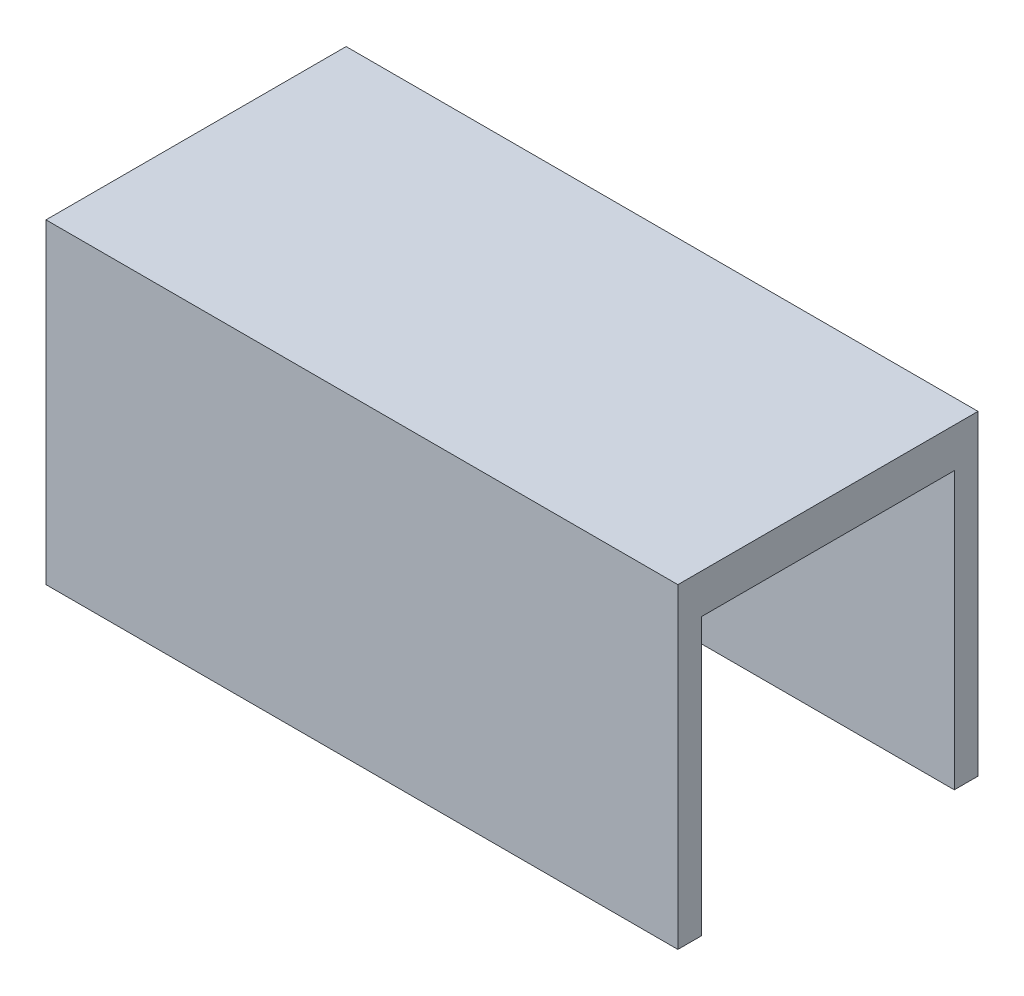
SolidWorks part; units mm, degrees
ref_plane "Front Plane" through (0, 0, 0) normal (0, 0, 1) x (1, 0, 0)
ref_plane "Top Plane" through (0, 0, 0) normal (0, 1, 0) x (1, 0, 0)
ref_plane "Right Plane" through (0, 0, 0) normal (1, 0, 0) x (0, 0, -1)
sketch "Sketch1" plane through (0, 0, 0) normal (1, 0, 0) x (0, 0, -1)
  line L0 (-8, 0) -> (-8, 17.5)
  line L1 (-8, 17.5) -> (8, 17.5)
  line L2 (8, 17.5) -> (8, 0)
  line L3 (8, 0) -> (9.5, 0)
  line L4 (9.5, 0) -> (9.5, 20)
  line L5 (9.5, 20) -> (-9.5, 20)
  line L6 (-9.5, 20) -> (-9.5, 0)
  line L7 (-9.5, 0) -> (-8, 0)
  point P9 (0, 20)
  point P10 (0, 17.5)
  dimension "D1" = 16
  dimension "D2" = 19
  dimension "D3" = 2.5
  dimension "D4" = 20
extrude "Boss-Extrude1" add sketch "Sketch1" along normal mid plane 40
sketch "Sketch2" plane through (0, 0, 8) normal (0, 0, -1) x (-1, 0, 0)
  line L1 (20, 0) -> (20, 20) construction
  line L3 (20, 17.5) -> (20, 20)
  line L5 (-20, 17.5) -> (-20, 20)
  line L6 (-20, 0) -> (-20, 20) construction
  line L7 (20, 20) -> (-20, 20)
  line L8 (-20, 17.5) -> (0, 0) construction
  line L9 (0, 0) -> (20, 17.5) construction
  arc A0 (-20, 17.5) -> (20, 17.5) centre (0, 40.3571) ccw
  dimension "D1" = 2.5
extrude "Boss-Extrude2" add sketch "Sketch2" along normal up to next
